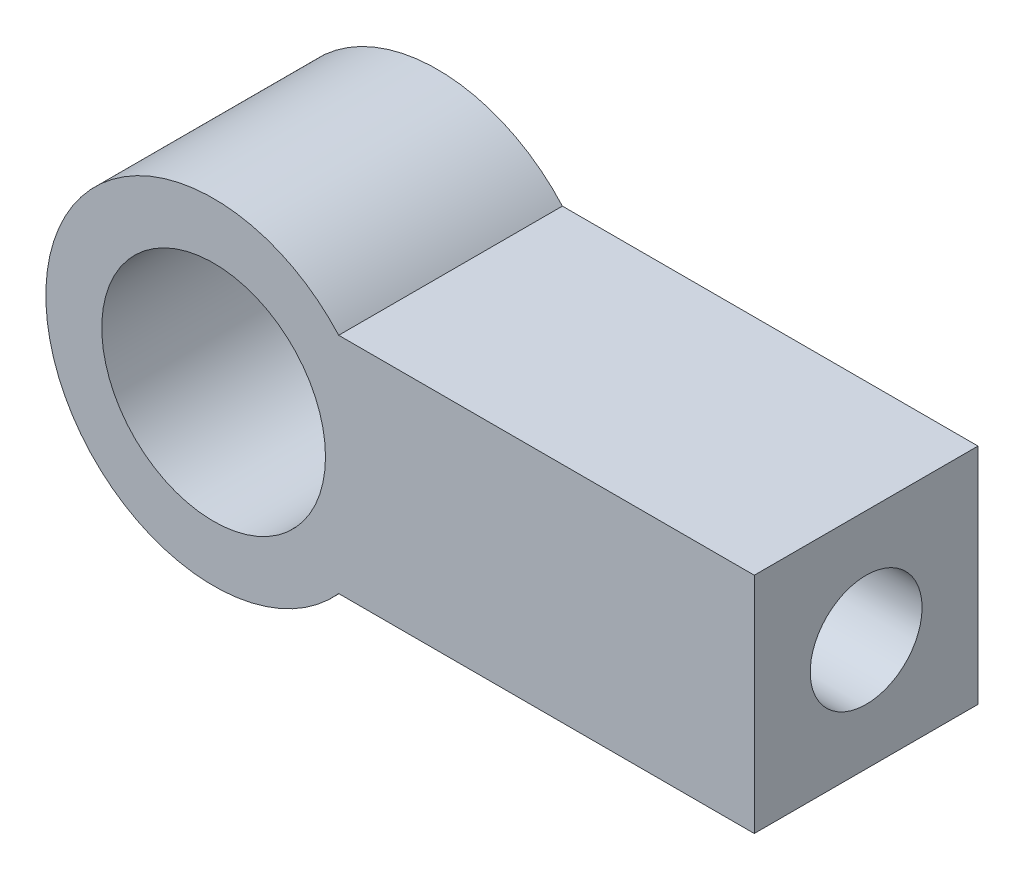
SolidWorks part; units mm, degrees
ref_plane "Top Plane" through (0, 0, 0) normal (0, 0, 1) x (1, 0, 0)
ref_plane "Right Plane" through (0, 0, 0) normal (0, 1, 0) x (1, 0, 0)
ref_plane "Front Plane" through (0, 0, 0) normal (1, 0, 0) x (0, 0, -1)
sketch "Sketch1" plane through (0, 0, 0) normal (0, 0, 1) x (1, 0, 0)
  line L0 (0, 0) -> (14.5, 0) construction
  line L1 (3.3541, -3) -> (14.5, -3)
  line L2 (14.5, -3) -> (14.5, 3)
  line L3 (3.3541, 3) -> (14.5, 3)
  line L4 (2.5981, -1.5) -> (14.5, -1.5) construction
  line L5 (2.5981, 1.5) -> (14.5, 1.5) construction
  circle A0 centre (0, 0) radius 3 construction
  arc A1 (3.3541, 3) -> (3.3541, -3) centre (0, 0) ccw
  point P12 (-4.5, 0)
  dimension "D1" = 6
  dimension "D2" = 9
  dimension "D3" = 6
  dimension "D4" = 3
  dimension "D5" = 19
extrude "Boss-Extrude1" add sketch "Sketch1" along normal mid plane 6
sketch "Sketch10" plane through (0, 0, 3) normal (0, 0, 1) x (1, 0, 0)
  circle A0 centre (0, 0) radius 3
  circle A1 centre (0, 0) radius 3 construction
extrude "Cut-Extrude1" cut sketch "Sketch10" against normal through all both and the other way through all
ref_plane "Plane1" through (-4.5, 0, 0) normal (-1, 0, 0) x (0, 0, 1)
sketch "Sketch11" plane through (14.5, 0, 0) normal (1, 0, 0) x (0, 0, -1)
  line L0 (0, 4.5) -> (0, -4.5) construction
  circle A0 centre (0, 0) radius 1.5
  dimension "D1" = 3
extrude "Cut-Extrude2" cut sketch "Sketch11" against normal offset from surface (9 mm away) 10 up to plane "Plane1"
